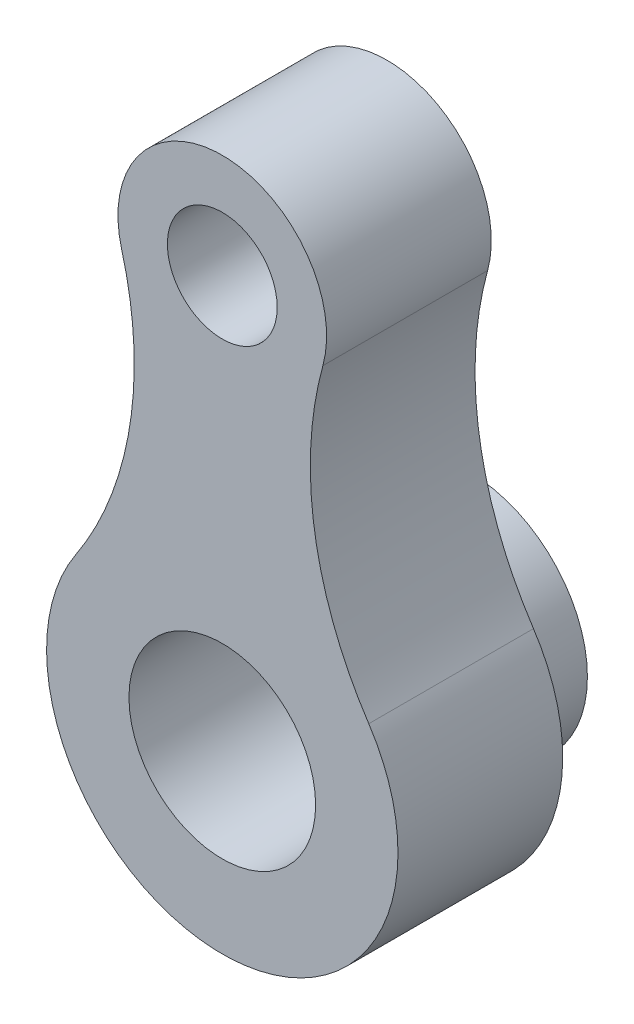
SolidWorks part; units mm, degrees
ref_plane "Ön Düzlem" through (0, 0, 0) normal (0, 0, 1) x (1, 0, 0)
ref_plane "Üst Düzlem" through (0, 0, 0) normal (0, 1, 0) x (1, 0, 0)
ref_plane "Sağ Düzlem" through (0, 0, 0) normal (1, 0, 0) x (0, 0, -1)
sketch "Çizim1" plane through (0, 0, 0) normal (0, 0, 1) x (1, 0, 0)
  circle A0 centre (0, -30.0435) radius 32
  circle A1 centre (0, -30.0435) radius 27.5
  circle A2 centre (0, -30.0435) radius 21.5
  circle A3 centre (0, -30.0435) radius 17
  circle A4 centre (0, 44.9565) radius 10
  circle A5 centre (0, 44.9565) radius 19
  arc A6 (-26.6783, -12.3724) -> (-18.3212, 39.9234) centre (-80.0349, 22.9698) ccw
  arc A7 (26.6783, -12.3724) -> (18.3212, 39.9234) centre (80.0349, 22.9698) cw
  point P5 (0, 0)
  dimension "D1" = 34
  dimension "D2" = 43
  dimension "D3" = 55
  dimension "D4" = 64
  dimension "D5" = 20
  dimension "D6" = 38
  dimension "D7" = 75
  dimension "D8" = 128
extrude "Yükseklik-Ekstrüzyon1" add sketch "Çizim1" along normal blind 15 and the other way blind 15 contours A0 A7 A5 A6 | A0 | A5 region at (0, 13.3542, 0)
extrude "Kes-Ekstrüzyon2" cut sketch "Çizim1<8>" against normal blind 39 from offset 10 contours A1 A2 region at (-26.7222, -30.0435, 0) offset against normal yes
sketch "Çizim1<8>" plane through (0, 0, 0) normal (0, 0, 1) x (1, 0, 0) same geometry as "Çizim1"
extrude "Yükseklik-Ekstrüzyon4" add sketch "Çizim1<11>" against normal blind 30 contours A2 A3 | A3 region at (-20.8919, -30.0435, 0) region at (0, -30.0435, 0)
sketch "Çizim1<11>" plane through (0, 0, 0) normal (0, 0, 1) x (1, 0, 0) same geometry as "Çizim1"
extrude "Kes-Ekstrüzyon3" cut sketch "Çizim1<12>" against normal blind 47 and the other way blind 26 contours A3 region at (0, -30.0435, 0)
sketch "Çizim1<12>" plane through (0, 0, 0) normal (0, 0, 1) x (1, 0, 0) same geometry as "Çizim1"
extrude "Kes-Ekstrüzyon4" cut sketch "Çizim1<13>" against normal blind 47 and the other way blind 47 contours A4 region at (0, 44.9565, 0)
sketch "Çizim1<13>" plane through (0, 0, 0) normal (0, 0, 1) x (1, 0, 0) same geometry as "Çizim1"
